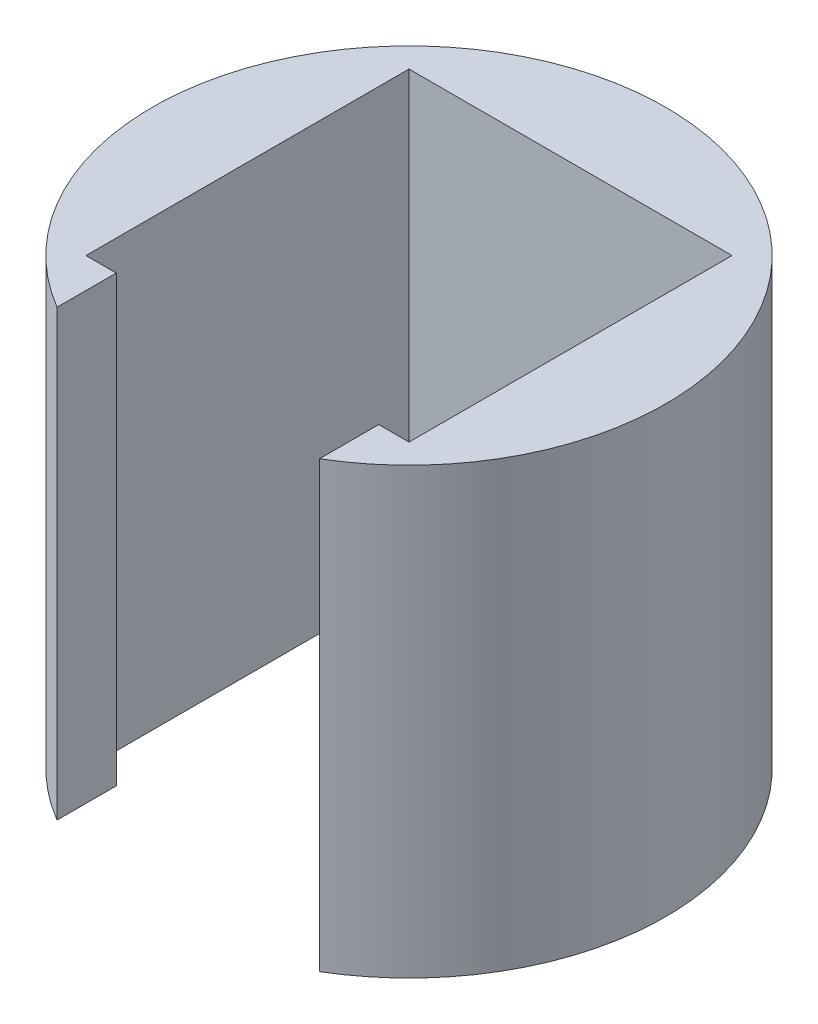
SolidWorks part; units mm, degrees
ref_plane "Front Plane" through (0, 0, 0) normal (0, 0, 1) x (1, 0, 0)
ref_plane "Top Plane" through (0, 0, 0) normal (0, 1, 0) x (1, 0, 0)
ref_plane "Right Plane" through (0, 0, 0) normal (1, 0, 0) x (0, 0, -1)
sketch "Sketch2" plane through (0, 0, 0) normal (0, 1, 0) x (1, 0, 0)
  line L0 (-8, -8) -> (-6.5, -8)
  line L1 (-8, 8) -> (8, 8)
  line L2 (-8, 8) -> (-8, -8)
  line L3 (-8, -8) -> (8, -8)
  line L4 (8, 8) -> (8, -8)
  line L5 (-8, 8) -> (8, -8) construction
  line L6 (-8, -8) -> (8, 8) construction
  line L7 (-6.5, -8) -> (-6.5, -10.9338)
  line L9 (6.5, -10.9338) -> (6.5, -8)
  line L10 (6.5, -8) -> (8, -8)
  arc A0 (6.5, -10.9338) -> (-6.5, -10.9338) centre (0, 0) ccw
extrude "Boss-Extrude3" add sketch "Sketch2" along normal blind 22 contours L9 A0 L7 L0 L2 L1 L4 L3 region at (-7.25, 0, 8.3474)
